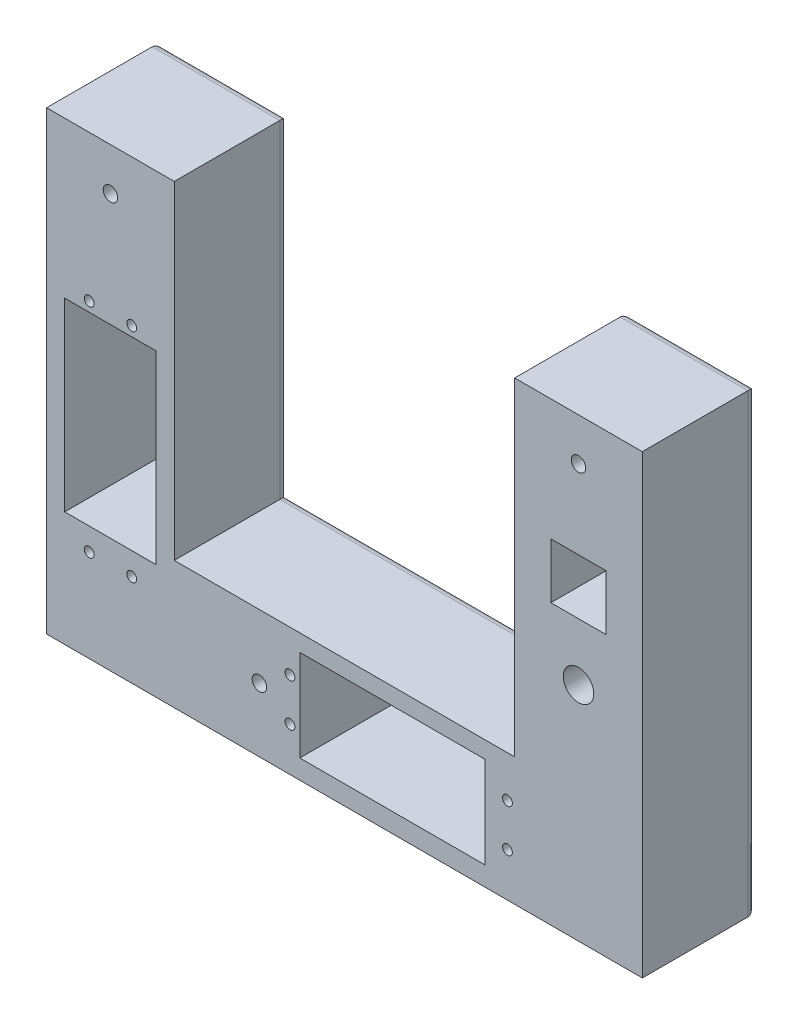
SolidWorks part; units mm, degrees
ref_plane "Front Plane" through (0, 0, 0) normal (0, 0, 1) x (1, 0, 0)
ref_plane "Top Plane" through (0, 0, 0) normal (0, 1, 0) x (1, 0, 0)
ref_plane "Right Plane" through (0, 0, 0) normal (1, 0, 0) x (0, 0, -1)
sketch "Sketch1" plane through (0, 0, 0) normal (0, 0, 1) x (1, 0, 0)
  line L0 (115.7962, 12.865) -> (115.7962, 120) construction
  line L1 (85.7962, 12.865) -> (115.7962, 12.865)
  line L2 (85.7962, 42.865) -> (85.7962, 120)
  line L3 (85.7962, 120) -> (115.7962, 120)
  line L4 (115.7962, 12.865) -> (115.7962, 120)
  line L5 (5.7962, 120) -> (-24.2038, 120)
  line L6 (5.7962, 120) -> (5.7962, 42.865)
  line L7 (5.7962, 12.865) -> (-24.2038, 12.865)
  line L8 (-24.2038, 120) -> (-24.2038, 12.865)
  line L9 (5.7962, 12.865) -> (85.7962, 12.865)
  line L10 (-24.2038, 12.865) -> (115.7962, 12.865) construction
  line L11 (5.7962, 42.865) -> (85.7962, 42.865)
  dimension "D1" = 80
  dimension "D2" = 30
  dimension "D3" = 30
  dimension "D4" = 107.135
  dimension "D5" = 107.135
  dimension "D6" = 140
  dimension "D7" = 30
extrude "Boss-Extrude1" add sketch "Sketch1" along normal blind 26.8 contours L6 L11 L2 L3 L4 L1 L9 L7 L8 L5
sketch "Sketch2" plane through (0, 0, 26.8) normal (0, 0, 1) x (1, 0, 0)
  line L0 (45.7962, 12.865) -> (45.7962, 163.1977) construction
  line L1 (115.7962, 12.865) -> (-24.2038, 12.865) construction
  line L2 (-24.2038, 87.865) -> (115.7962, 87.865) construction
  line L3 (-24.2038, 120) -> (-24.2038, 12.865) construction
  line L4 (115.7962, 12.865) -> (115.7962, 120) construction
  line L5 (-9.2038, 120) -> (-9.2038, 12.865) construction
  line L6 (-19.9538, 83.365) -> (1.5462, 83.365)
  line L7 (-19.9538, 83.365) -> (-19.9538, 39.865)
  line L8 (-19.9538, 39.865) -> (1.5462, 39.865)
  line L9 (1.5462, 83.365) -> (1.5462, 39.865)
  line L10 (35.2962, 38.8955) -> (78.7962, 38.8955)
  line L11 (35.2962, 38.8955) -> (35.2962, 17.3955)
  line L12 (35.2962, 17.3955) -> (78.7962, 17.3955)
  line L13 (78.7962, 38.8955) -> (78.7962, 17.3955)
  line L14 (5.7962, 120) -> (-24.2038, 120) construction
  line L15 (-24.2038, 28.1455) -> (115.7962, 28.1455) construction
  dimension "D1" = 75
  dimension "D2" = 48
  dimension "D3" = 21.5
  dimension "D4" = 43.5
  dimension "D5" = 21.5
  dimension "D6" = 43.5
  dimension "D7" = 33
  dimension "D8" = 10.75
  dimension "D9" = 10.75
extrude "Cut-Extrude1" cut sketch "Sketch2" against normal through all
sketch "Sketch3" plane through (0, 0, 26.8) normal (0, 0, 1) x (1, 0, 0)
  line L0 (-19.9538, 39.865) -> (1.5462, 39.865) construction
  line L1 (-9.2038, 83.365) -> (-9.2038, -3.066) construction
  line L2 (1.5462, 83.365) -> (-19.9538, 83.365) construction
  circle A0 centre (-14.2038, 34.565) radius 1.15
  circle A1 centre (-4.2038, 34.565) radius 1.15
  circle A2 centre (-14.2038, 85.665) radius 1.15
  circle A3 centre (-4.2038, 85.665) radius 1.15
  dimension "D3" = 2.3
  dimension "D4" = 2.3
  dimension "D7" = 2.3
  dimension "D1" = 5.3
  dimension "D2" = 5.3
  dimension "D5" = 10
  dimension "D6" = 5
  dimension "D8" = 2.3
  dimension "D9" = 5
extrude "Boss-Extrude2" add sketch "Sketch3" against normal through all
extrude "Cut-Extrude2" cut sketch "Sketch3<2>" against normal through all
sketch "Sketch3<2>" plane through (0, 0, 26.8) normal (0, 0, 1) x (1, 0, 0) same geometry as "Sketch3"
sketch "Sketch4" plane through (0, 0, 26.8) normal (0, 0, 1) x (1, 0, 0)
  line L0 (35.2962, 28.1455) -> (128.9839, 28.1455) construction
  line L1 (35.2962, 38.8955) -> (35.2962, 17.3955) construction
  line L2 (78.7962, 17.3955) -> (78.7962, 38.8955) construction
  circle A0 centre (84.0962, 23.1455) radius 1.15
  circle A1 centre (84.0962, 33.1455) radius 1.15
  circle A2 centre (32.9962, 23.1455) radius 1.15
  circle A3 centre (32.9962, 33.1455) radius 1.15
  dimension "D1" = 2.3
  dimension "D4" = 2.3
  dimension "D2" = 5.3
  dimension "D3" = 5
  dimension "D5" = 2.3
  dimension "D6" = 5
extrude "Cut-Extrude3" cut sketch "Sketch4" against normal through all
fillet "Fillet2" radius 2 8 edges at (45.7962, 12.865, 0) (115.7962, 66.4325, 0) (100.7962, 120, 0) (85.7962, 81.4325, 0) (45.7962, 42.865, 0) (5.7962, 81.4325, 0) (-9.2038, 120, 0) (-24.2038, 66.4325, 0)
hole_wizard "CBORE for M3 SHCS1" positions "Sketch11" profile "Sketch10" counterbore size "M3" standard "ANSI Metric" end condition through all
sketch "Sketch11" plane through (0, 0, 0) normal (0, 0, -1) x (-1, 0, 0)
  line L0 (-100.7962, 120) -> (-100.7962, 12.865) construction
  line L1 (-115.7962, 120) -> (-85.7962, 120) construction
  line L2 (24.2038, 12.865) -> (-115.7962, 12.865) construction
  line L4 (-82.3394, 42.865) -> (-82.3394, 12.865) construction
  line L5 (-85.7962, 42.865) -> (-5.7962, 42.865) construction
  line L7 (-82.3394, 27.865) -> (24.2038, 27.865) construction
  line L8 (24.2038, 120) -> (24.2038, 12.865) construction
  line L10 (9.2038, 120) -> (9.2038, 12.865) construction
  line L11 (-5.7962, 120) -> (24.2038, 120) construction
  point P0 (-25.7962, 27.865)
  point P2 (9.2038, 110)
  point P4 (-100.7962, 110)
  dimension "D1" = 10
  dimension "D2" = 10
  dimension "D3" = 50
sketch "Sketch10" plane through (25.7962, 27.865, 0) normal (1, 0, 0) x (0, 1, 0)
  line L0 (0, 0) -> (0, 26.8)
  line L1 (0, 26.8) -> (1.7, 26.8)
  line L3 (1.7, 26.8) -> (1.7, 3)
  line L4 (1.7, 3) -> (3.25, 3)
  line L5 (3.25, 3) -> (3.25, 0)
  line L7 (3.25, 0) -> (0, 0)
  line L11 (0, -6.35) -> (0, 107.95) construction
  dimension "Thru Hole Dia." = 3.4
  dimension "Thru Hole Depth" = 26.8
  dimension "C'Bore Dia." = 6.5
  dimension "C'Bore Depth" = 3
sketch "Sketch12" plane through (0, 0, 0) normal (0, 0, -1) x (-1, 0, 0)
  line L0 (-100.7962, 120) -> (-100.7962, 12.865) construction
  line L1 (-115.7962, 120) -> (-85.7962, 120) construction
  line L2 (24.2038, 12.865) -> (-115.7962, 12.865) construction
  line L4 (-93.7962, 92) -> (-107.7962, 92)
  line L5 (-93.7962, 92) -> (-93.7962, 78)
  line L6 (-93.7962, 78) -> (-107.7962, 78)
  line L7 (-107.7962, 92) -> (-107.7962, 78)
  line L8 (-93.7962, 92) -> (-107.7962, 78) construction
  line L9 (-93.7962, 78) -> (-107.7962, 92) construction
  point P6 (-100.7962, 85)
  dimension "D1" = 14
  dimension "D2" = 35
extrude "Cut-Extrude5" cut sketch "Sketch12" against normal blind 10
sketch "Sketch13" plane through (0, 0, 10) normal (0, 0, -1) x (-1, 0, 0)
  line L0 (-93.7962, 78) -> (-93.7962, 92) construction
  line L1 (-107.2962, 78.5) -> (-94.2962, 78.5)
  line L2 (-107.2962, 78.5) -> (-107.2962, 91.5)
  line L3 (-107.2962, 91.5) -> (-94.2962, 91.5)
  line L4 (-94.2962, 78.5) -> (-94.2962, 91.5)
  line L5 (-107.2962, 78.5) -> (-94.2962, 91.5) construction
  line L6 (-107.2962, 91.5) -> (-94.2962, 78.5) construction
  line L8 (-93.7962, 92) -> (-107.7962, 92) construction
  point P0 (-100.7962, 85)
  dimension "D1" = 13
  dimension "D2" = 0.5
  dimension "D3" = 0.5
extrude "Cut-Extrude6" cut sketch "Sketch13" against normal through all
sketch "Sketch14" plane through (0, 0, 0) normal (0, 0, -1) x (-1, 0, 0)
  line L0 (-100.7962, 110) -> (-100.7962, 12.865) construction
  line L1 (24.2038, 12.865) -> (-115.7962, 12.865) construction
  line L2 (-115.7962, 120) -> (-85.7962, 120) construction
  circle A0 centre (-100.7962, 65) radius 3.585
  dimension "D1" = 7.17
  dimension "D2" = 55
extrude "Cut-Extrude7" cut sketch "Sketch14" against normal through all
